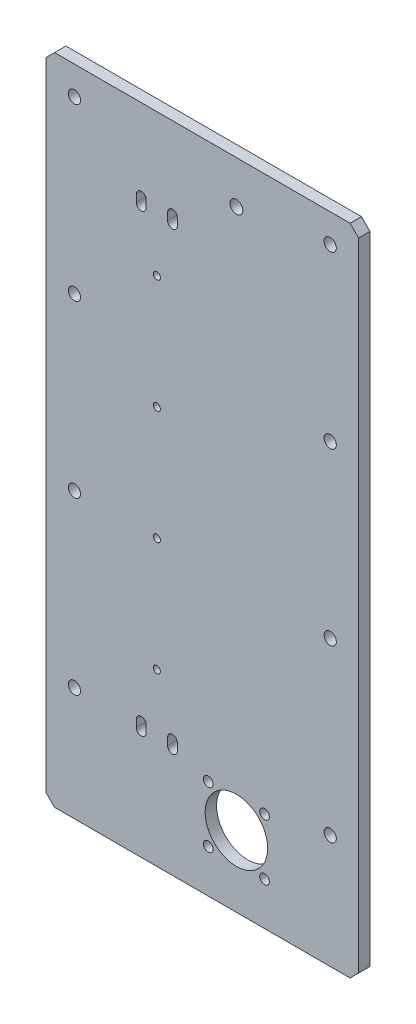
SolidWorks part; units mm, degrees
material "ABS PC"
ref_plane "Ebene vorne" through (0, 0, 0) normal (0, 0, 1) x (1, 0, 0)
ref_plane "Ebene oben" through (0, 0, 0) normal (0, 1, 0) x (1, 0, 0)
ref_plane "Ebene rechts" through (0, 0, 0) normal (1, 0, 0) x (0, 0, -1)
sketch "Skizze1" plane through (0, 0, 0) normal (0, 0, 1) x (1, 0, 0)
  line L1 (55, -115) -> (-55, -115)
  line L2 (55, -115) -> (55, 115)
  line L3 (55, 115) -> (-55, 115)
  line L4 (-55, -115) -> (-55, 115)
  line L5 (55, -115) -> (-55, 115) construction
  line L6 (55, 115) -> (-55, -115) construction
  point P0 (0, 0)
  dimension "D1" = 110
  dimension "D2" = 230
extrude "Aufsatz-Linear austragen1" add sketch "Skizze1" along normal blind 4
hole_wizard "M3 Gewindebohrung1" positions "Skizze2" profile "Skizze3" tap size "M3" standard "ISO" end condition through all
sketch "Skizze2" plane through (0, 0, 4) normal (0, 0, 1) x (1, 0, 0)
  line L0 (-16, 65) -> (-16, 25) construction
  line L3 (-16, -15) -> (-16, -55) construction
  line L5 (-16, 25) -> (-16, -15) construction
  line L7 (55, 115) -> (-55, 115) construction
  line L8 (-55, 115) -> (-55, -115) construction
  point P0 (-16, 65)
  point P2 (-16, 25)
  point P4 (-16, -15)
  point P6 (-16, -55)
  dimension "D1" = 40
  dimension "D2" = 50
  dimension "D3" = 39
sketch "Skizze3" plane through (-16, 65, 4) normal (1, 0, 0) x (0, -1, 0)
  line L0 (0, 0) -> (0, 4)
  line L1 (0, 4) -> (1.25, 4)
  line L2 (1.25, 4) -> (1.25, 0)
  line L5 (1.25, 0) -> (0, 0)
  line L11 (0, -6.35) -> (0, 107.95) construction
  dimension "Bohrerdurchmesser" = 2.5
  dimension "Bohrungstiefe" = 4
cosmetic thread "Bohrungsgewinde1" parameters "D2"=3
cosmetic thread "Bohrungsgewinde2" parameters "D2"=3
cosmetic thread "Bohrungsgewinde3" parameters "D2"=3
cosmetic thread "Bohrungsgewinde4" parameters "D2"=3
hole_wizard "Durchgangsloch für M41" positions "Skizze4" profile "Skizze5" hole size "M4" standard "ISO" end condition through all
sketch "Skizze4" plane through (0, 0, 4) normal (0, 0, 1) x (1, 0, 0)
  line L0 (-45, 105) -> (-45, 45) construction
  line L1 (-45, 45) -> (-45, -15) construction
  line L5 (45, -15) -> (45, 45) construction
  line L6 (45, 45) -> (45, 105) construction
  line L7 (45, 105) -> (-45, 105) construction
  line L9 (-45, 45) -> (45, 45) construction
  line L11 (45, -15) -> (-45, -15) construction
  line L17 (55, 115) -> (-55, 115) construction
  line L18 (45, -15) -> (45, -75) construction
  line L19 (45, -75) -> (-45, -75) construction
  line L20 (-45, -75) -> (-45, -15) construction
  line L21 (-55, 115) -> (-55, -115) construction
  line L22 (55, -115) -> (55, 115) construction
  point P0 (-45, 105)
  point P2 (45, 105)
  point P4 (-45, 45)
  point P6 (-45, -15)
  point P8 (45, 45)
  point P10 (45, -15)
  point P66 (45, -75)
  point P69 (-45, -75)
  dimension "D1" = 60
  dimension "D2" = 10
  dimension "D3" = 10
  dimension "D4" = 10
sketch "Skizze5" plane through (-45, 105, 4) normal (1, 0, 0) x (0, -1, 0)
  line L0 (0, 0) -> (0, 4)
  line L1 (0, 4) -> (2.15, 4)
  line L2 (2.15, 4) -> (2.15, 0)
  line L5 (2.15, 0) -> (0, 0)
  line L11 (0, -6.35) -> (0, 107.95) construction
  dimension "Bohrerdurchmesser" = 4.3
  dimension "Bohrungstiefe" = 4
hole_wizard "Durchgangsloch für M33" positions "Skizze6" profile "Skizze7" size "M3" standard "ISO" slot yes end condition through all
sketch "Skizze6" plane through (0, 0, 4) normal (0, 0, 1) x (1, 0, 0)
  line L0 (-21.5, 85) -> (-10.5, 85) construction
  line L1 (-10.5, 85) -> (-10.5, -75) construction
  line L2 (-10.5, -75) -> (-21.5, -75) construction
  line L3 (-21.5, -75) -> (-21.5, 85) construction
  line L5 (-16, -55) -> (-16, -75) construction
  line L7 (-21.5, -78) -> (-21.5, -72) construction
  circle A0 centre (-16, -55) radius 1.25 construction
  circle A1 centre (-16, 65) radius 1.25 construction
  point P0 (-21.5, -75)
  point P2 (-10.5, -75)
  point P4 (-21.5, 85)
  point P6 (-10.5, 85)
  dimension "D1" = 20
  dimension "D2" = 11
  dimension "D3" = 20
  dimension "D4" = 6
sketch "Skizze7" plane through (-21.5, -75, 4) normal (1, 0, 0) x (0, -1, 0)
  line L0 (0, 0) -> (0, 4)
  line L1 (0, 4) -> (1.7, 4)
  line L2 (1.7, 4) -> (1.7, 0)
  line L5 (1.7, 0) -> (0, 0)
  line L11 (0, -6.35) -> (0, 107.95) construction
  dimension "Bohrerdurchmesser" = 3.4
  dimension "Bohrungstiefe" = 4
hole_wizard "Durchgangsloch für M32" positions "Skizze8" profile "Skizze9" hole size "M3" standard "ISO" end condition through all
sketch "Skizze8" plane through (0, 0, 4) normal (0, 0, 1) x (1, 0, 0)
  line L1 (2.1005, -80.1005) -> (21.8995, -80.1005) construction
  line L2 (2.1005, -80.1005) -> (2.1005, -99.8995) construction
  line L3 (2.1005, -99.8995) -> (21.8995, -99.8995) construction
  line L4 (21.8995, -80.1005) -> (21.8995, -99.8995) construction
  circle A0 centre (12, -90) radius 14 construction
  circle A1 centre (-16, -55) radius 1.25 construction
  point P4 (2.1005, -80.1005)
  point P5 (21.8995, -99.8995)
  point P8 (2.1005, -99.8995)
  point P9 (21.8995, -80.1005)
  dimension "D1" = 28
  dimension "D3" = 28
  dimension "D2" = 35
sketch "Skizze9" plane through (21.8995, -80.1005, 4) normal (1, 0, 0) x (0, -1, 0)
  line L0 (0, 0) -> (0, 4)
  line L1 (0, 4) -> (1.7, 4)
  line L2 (1.7, 4) -> (1.7, 0)
  line L5 (1.7, 0) -> (0, 0)
  line L11 (0, -6.35) -> (0, 107.95) construction
  dimension "Bohrerdurchmesser" = 3.4
  dimension "Bohrungstiefe" = 4
sketch "Skizze10" plane through (0, 0, 4) normal (0, 0, 1) x (1, 0, 0)
  circle A0 centre (12, -90) radius 11
  dimension "D1" = 22
extrude "Schnitt-Linear austragen1" cut sketch "Skizze10" against normal through all
hole_wizard "Durchgangsloch für M42" positions "Skizze11" profile "Skizze12" hole size "M4" standard "ISO" end condition through all
sketch "Skizze11" plane through (0, 0, 4) normal (0, 0, 1) x (1, 0, 0)
  line L0 (12, -90) -> (12, 100) construction
  point P2 (12, 100)
  dimension "D1" = 190
sketch "Skizze12" plane through (12, 100, 4) normal (1, 0, 0) x (0, -1, 0)
  line L0 (0, 0) -> (0, 4)
  line L1 (0, 4) -> (2.25, 4)
  line L2 (2.25, 4) -> (2.25, 0)
  line L5 (2.25, 0) -> (0, 0)
  line L11 (0, -6.35) -> (0, 107.95) construction
  dimension "Bohrerdurchmesser" = 4.5
  dimension "Bohrungstiefe" = 4
chamfer "Fase1" distance 3 angle 45 4 edges at (55, -115, 2) (-55, -115, 2) (55, 115, 2) (-55, 115, 2)
